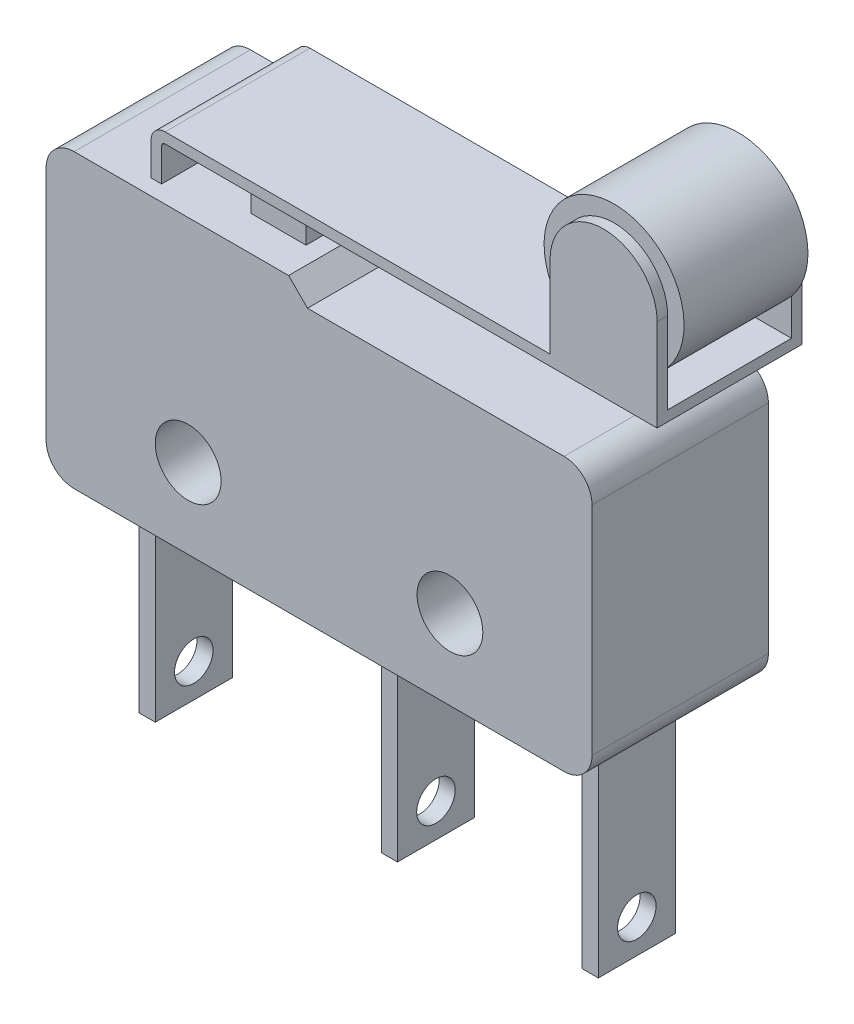
SolidWorks part; units mm, degrees
ref_plane "Front Plane" through (0, 0, 0) normal (0, 0, 1) x (1, 0, 0)
ref_plane "Top Plane" through (0, 0, 0) normal (0, 1, 0) x (1, 0, 0)
ref_plane "Right Plane" through (0, 0, 0) normal (1, 0, 0) x (0, 0, -1)
sketch "Sketch1" plane through (0, 0, 0) normal (0, 0, 1) x (1, 0, 0)
  line L0 (8.8011, 10.5918) -> (9.4869, 9.906)
  line L1 (1.016, 0) -> (1.5748, 0)
  line L2 (0, 1.016) -> (0, 9.5758)
  line L3 (1.016, 10.5918) -> (6.1595, 10.5918)
  line L4 (19.812, 1.016) -> (19.812, 8.89)
  line L5 (9.4869, 9.906) -> (18.796, 9.906)
  line L6 (6.1595, 10.5918) -> (6.1595, 11.5744)
  line L7 (6.1595, 11.8872) -> (8.1661, 11.8872) construction
  line L8 (8.1661, 11.5744) -> (8.1661, 10.5918)
  line L9 (7.1628, 11.8872) -> (7.1628, 6.512) construction
  line L10 (8.1661, 10.5918) -> (8.8011, 10.5918)
  line L11 (1.8669, -7.8486) -> (1.8669, -10.4767) construction
  line L12 (10.9474, 0) -> (17.653, 0)
  line L13 (1.5748, 0) -> (1.5748, -7.8486)
  line L14 (1.5748, -7.8486) -> (2.159, -7.8486)
  line L15 (2.159, 0) -> (2.159, -7.8486)
  line L16 (18.2372, 0) -> (18.796, 0)
  line L17 (10.3632, 0) -> (10.3632, -7.8486)
  line L18 (10.3632, -7.8486) -> (10.9474, -7.8486)
  line L19 (10.9474, 0) -> (10.9474, -7.8486)
  line L21 (17.653, 0) -> (17.653, -7.8486)
  line L22 (17.653, -7.8486) -> (18.2372, -7.8486)
  line L23 (18.2372, 0) -> (18.2372, -7.8486)
  line L24 (10.6553, -7.8486) -> (10.6553, -10.4767) construction
  line L25 (17.9451, -7.8486) -> (17.9451, -10.4767) construction
  line L26 (2.159, 0) -> (10.3632, 0)
  circle A0 centre (5.1562, 2.8956) radius 1.1938
  circle A1 centre (14.6558, 2.8956) radius 1.1938
  arc A2 (18.796, 9.906) -> (19.812, 8.89) centre (18.796, 8.89) cw
  arc A3 (18.796, 0) -> (19.812, 1.016) centre (18.796, 1.016) ccw
  arc A4 (1.016, 0) -> (0, 1.016) centre (1.016, 1.016) cw
  arc A5 (0, 9.5758) -> (1.016, 10.5918) centre (1.016, 9.5758) cw
  arc A6 (6.235, 11.6904) -> (8.0906, 11.6904) centre (7.1628, 9.6012) cw
  arc A7 (8.0906, 11.6904) -> (8.1661, 11.5744) centre (8.0391, 11.5744) cw
  arc A8 (6.235, 11.6904) -> (6.1595, 11.5744) centre (6.2865, 11.5744) ccw
  point P19 (19.812, 9.906)
  point P22 (19.812, 0)
  point P25 (0, 0)
  point P28 (0, 10.5918)
  dimension "D3" = 2.3876
  dimension "D13" = 1.016
  dimension "D18" = 2.286
  dimension "D19" = 0.127
  dimension "D1" = 19.812
  dimension "D2" = 10.5918
  dimension "D4" = 9.4996
  dimension "D5" = 2.8956
  dimension "D6" = 9.906
  dimension "D7" = 45
  dimension "D8" = 5.1562
  dimension "D9" = 8.9916
  dimension "D10" = 2.0066
  dimension "D11" = 2.0066
  dimension "D12" = 0.635
  dimension "D14" = 0.5842
  dimension "D15" = 7.8486
  dimension "D16" = 8.7884
  dimension "D17" = 7.2898
extrude "Boss-Extrude1" add sketch "Sketch1" along normal blind 6.4008
sketch "Sketch2" plane through (0, 0, 0) normal (-1, 0, 0) x (0, 0, 1)
  line L0 (6.4008, 11.8872) -> (0, 11.8872) construction
  line L1 (0, 10.5918) -> (0.762, 10.5918)
  line L2 (0, 10.5918) -> (0, 11.8872)
  line L3 (0, 11.8872) -> (0.762, 11.8872)
  line L4 (0.762, 10.5918) -> (0.762, 11.8872)
  line L5 (3.2004, -7.8486) -> (3.2004, 0) construction
  line L6 (6.4008, 10.5918) -> (5.1308, 10.5918)
  line L7 (6.4008, 10.5918) -> (6.4008, 11.8872)
  line L8 (6.4008, 11.8872) -> (5.1308, 11.8872)
  line L9 (5.1308, 10.5918) -> (5.1308, 11.8872)
  line L10 (6.4008, -7.8486) -> (4.5974, -7.8486)
  line L11 (6.4008, -7.8486) -> (6.4008, -0.508)
  line L12 (6.4008, -0.508) -> (4.5974, -0.508)
  line L13 (4.5974, -7.8486) -> (4.5974, -0.508)
  line L14 (0, -7.8486) -> (1.8034, -7.8486)
  line L15 (0, -7.8486) -> (0, -0.508)
  line L16 (0, -0.508) -> (1.8034, -0.508)
  line L17 (1.8034, -7.8486) -> (1.8034, -0.508)
  line L18 (6.4008, -7.8486) -> (0, -7.8486) construction
  line L19 (6.4008, 0) -> (0, 0) construction
  line L20 (6.4008, 0) -> (0, 0) construction
  line L21 (0, -0.508) -> (1.5494, -0.508)
  line L22 (0, -0.508) -> (0, 0)
  line L23 (0, 0) -> (1.5494, 0)
  line L24 (1.5494, -0.508) -> (1.5494, 0)
  line L26 (6.4008, -0.508) -> (4.8514, -0.508)
  line L27 (6.4008, -0.508) -> (6.4008, 0)
  line L28 (6.4008, 0) -> (4.8514, 0)
  line L29 (4.8514, -0.508) -> (4.8514, 0)
  circle A0 centre (3.2004, -6.4516) radius 0.6985
  dimension "D6" = 1.397
  dimension "D1" = 2.794
  dimension "D2" = 0.254
  dimension "D3" = 0.508
  dimension "D4" = 0.762
  dimension "D5" = 1.27
  dimension "D7" = 1.397
extrude "Cut-Extrude1" cut sketch "Sketch2" against normal through all contours L14 L17 L16 L15 | L13 L10 L11 L12 | L9 L6 L7 L8 | A0 | L27 L28 L29 L26 | L22 L23 L24 L21 | L2 L3 L4 L1 region at (0, 11.2395, 5.7658) region at (0, -4.1783, 5.4991) region at (0, -4.1783, 0.9017)
chamfer "Chamfer1" distance 0.1778 angle 45 12 edges at (17.9451, -7.8486, 4.5974) (18.2372, -7.8486, 3.2004) (17.9451, -7.8486, 1.8034) (17.653, -7.8486, 3.2004) (10.6553, -7.8486, 4.5974) (10.9474, -7.8486, 3.2004) (10.6553, -7.8486, 1.8034) (10.3632, -7.8486, 3.2004) (1.8669, -7.8486, 4.5974) (2.159, -7.8486, 3.2004) (1.8669, -7.8486, 1.8034) (1.5748, -7.8486, 3.2004)
sketch "Sketch3" plane through (0, 0, 6.4008) normal (0, 0, 1) x (1, 0, 0)
  line L0 (3.2385, 10.5918) -> (3.2385, 11.7856)
  line L1 (8.8011, 10.5918) -> (1.016, 10.5918) construction
  line L2 (3.7465, 12.2936) -> (17.7165, 12.2936)
  line L3 (21.6027, 12.2936) -> (21.6027, 11.9126)
  line L4 (21.6027, 11.9126) -> (3.7465, 11.9126)
  line L5 (3.6195, 11.7856) -> (3.6195, 10.5918)
  line L6 (3.2385, 10.5918) -> (3.6195, 10.5918)
  line L7 (6.1595, 11.5744) -> (6.1595, 10.5918) construction
  line L8 (21.6027, 12.2936) -> (21.6027, 13.6198)
  line L9 (17.7165, 13.6198) -> (21.6027, 13.6198) construction
  line L10 (17.7165, 13.6198) -> (17.7165, 12.2936)
  line L11 (19.6596, 15.2556) -> (19.6596, 13.6198) construction
  line L12 (13.7612, 17.7956) -> (19.6399, 17.7956) construction
  arc A1 (21.6027, 13.6198) -> (17.7165, 13.6198) centre (19.6596, 15.2556) ccw
  circle A2 centre (14.6558, 2.8956) radius 1.1938 construction
  circle A3 centre (5.1562, 2.8956) radius 1.1938 construction
  arc A4 (3.7465, 11.9126) -> (3.6195, 11.7856) centre (3.7465, 11.7856) ccw
  arc A5 (3.2385, 11.7856) -> (3.7465, 12.2936) centre (3.7465, 11.7856) cw
  arc A6 (8.0906, 11.6904) -> (6.235, 11.6904) centre (7.1628, 9.6012) ccw construction
  dimension "D6" = 5.08
  dimension "D7" = 0.127
  dimension "D8" = 2.3114
  dimension "D1" = 0.381
  dimension "D2" = 2.54
  dimension "D3" = 14.9
  dimension "D4" = 14.5034
  dimension "D5" = 3.8862
extrude "Boss-Extrude3" add sketch "Sketch3" against normal through all
sketch "Sketch4" plane through (19.812, 0, 0) normal (1, 0, 0) x (0, 0, -1)
  line L0 (0, 17.7956) -> (-6.4008, 17.7956) construction
  line L1 (0, 10.5918) -> (-0.5715, 10.5918)
  line L2 (0, 10.5918) -> (0, 17.7956)
  line L3 (0, 17.7956) -> (-0.5715, 17.7956)
  line L4 (-0.5715, 10.5918) -> (-0.5715, 17.7956)
  line L5 (-0.762, 10.5918) -> (-0.762, 11.5744) construction
  line L6 (-6.4008, 10.5918) -> (-5.8293, 10.5918)
  line L7 (-6.4008, 10.5918) -> (-6.4008, 17.7956)
  line L8 (-6.4008, 17.7956) -> (-5.8293, 17.7956)
  line L9 (-5.8293, 10.5918) -> (-5.8293, 17.7956)
  dimension "D1" = 0.1905
extrude "Cut-Extrude2" cut sketch "Sketch4" against normal through all and the other way through all
sketch "Sketch5" plane through (0, 0, 5.8293) normal (0, 0, 1) x (1, 0, 0)
  line L0 (21.6027, 11.9126) -> (21.6027, 13.6198) construction
  line L1 (21.6027, 13.6198) -> (21.6027, 15.2556)
  line L2 (17.7165, 13.6198) -> (17.7165, 15.2556)
  arc A0 (21.6027, 15.2556) -> (17.7165, 15.2556) centre (19.6596, 15.2556) ccw
  arc A1 (21.6027, 13.6198) -> (17.7165, 13.6198) centre (19.6596, 15.2556) ccw
extrude "Cut-Extrude3" cut sketch "Sketch5" against normal blind 0.381
sketch "Sketch6" plane through (0, 0, 0.5715) normal (0, 0, -1) x (-1, 0, 0)
  line L0 (-21.6027, 15.2556) -> (-21.6027, 13.6198)
  line L1 (-17.7165, 15.2556) -> (-17.7165, 13.6198)
  arc A0 (-17.7165, 13.6198) -> (-21.6027, 13.6198) centre (-19.6596, 15.2556) ccw construction
  arc A1 (-17.7165, 15.2556) -> (-21.6027, 15.2556) centre (-19.6596, 15.2556) ccw construction
  arc A2 (-17.7165, 13.6198) -> (-21.6027, 13.6198) centre (-19.6596, 15.2556) ccw
  arc A3 (-17.7165, 15.2556) -> (-21.6027, 15.2556) centre (-19.6596, 15.2556) ccw
extrude "Cut-Extrude4" cut sketch "Sketch6" against normal blind 0.381
sketch "Sketch7" plane through (0, 0, 0.5715) normal (0, 0, -1) x (-1, 0, 0)
  line L0 (-21.6027, 13.6198) -> (-21.6027, 12.2936)
  line L1 (-21.6027, 15.2556) -> (-21.6027, 11.9126) construction
  line L2 (-21.6027, 12.2936) -> (-17.7165, 12.2936)
  line L3 (-17.7165, 12.2936) -> (-17.7165, 13.6198)
  line L4 (-17.7165, 12.2936) -> (-17.7165, 15.2556) construction
  line L5 (-3.7465, 12.2936) -> (-17.7165, 12.2936) construction
  arc A0 (-21.6027, 13.6198) -> (-17.7165, 13.6198) centre (-19.6596, 15.2556) ccw
  arc A1 (-17.7165, 13.6198) -> (-21.6027, 13.6198) centre (-19.6596, 15.2556) ccw construction
extrude "Cut-Extrude5" cut sketch "Sketch7" against normal offset from surface (4.4958 mm away) 0.381 from offset 0.381 up to face at (9.9716, 12.5753, 5.8293) offset against normal yes
ref_axis "Axis2" through (19.6596, 17.1987, 5.8293) along (0, 1, 0)
